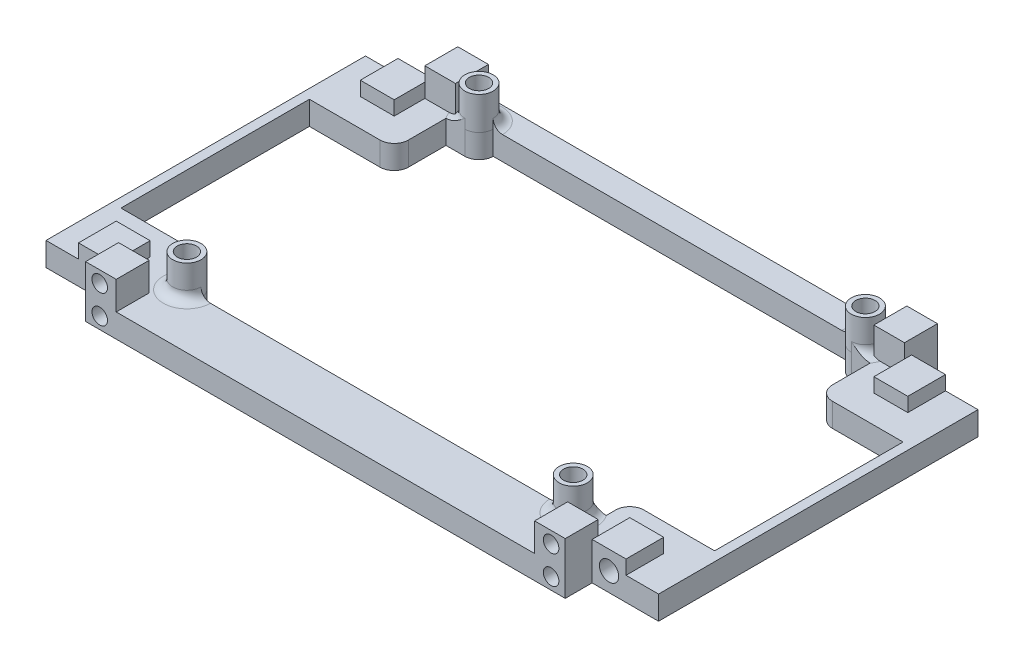
SolidWorks part; units mm, degrees
ref_plane "Front Plane" through (0, 0, 0) normal (0, 0, 1) x (1, 0, 0)
ref_plane "Top Plane" through (0, 0, 0) normal (0, 1, 0) x (1, 0, 0)
ref_plane "Right Plane" through (0, 0, 0) normal (1, 0, 0) x (0, 0, -1)
sketch "Sketch1" plane through (0, 0, 0) normal (0, 1, 0) x (1, 0, 0)
  line L0 (-65, -33.9) -> (-65, 33.9)
  line L1 (-65, -41) -> (65, -41) construction
  line L2 (-65, -41) -> (-65, 41) construction
  line L3 (-65, 41) -> (65, 41) construction
  line L4 (65, -41) -> (65, 41) construction
  line L5 (-65, -41) -> (65, 41) construction
  line L6 (-65, 41) -> (65, -41) construction
  line L7 (-65, 33.9) -> (-50.9, 33.9)
  line L8 (-50.9, 33.9) -> (-50.9, 41)
  line L9 (-50.9, 41) -> (50.9, 41)
  line L10 (50.9, 41) -> (50.9, 33.9)
  line L11 (50.9, 33.9) -> (65, 33.9)
  line L12 (65, 33.9) -> (65, -33.9)
  line L13 (65, -33.9) -> (50.9, -33.9)
  line L14 (50.9, -33.9) -> (50.9, -41)
  line L15 (50.9, -41) -> (-50.9, -41)
  line L16 (-50.9, -41) -> (-50.9, -33.9)
  line L17 (-50.9, -33.9) -> (-65, -33.9)
  point P0 (0, 0)
  dimension "D1" = 130
  dimension "D2" = 82
  dimension "D3" = 7.1
  dimension "D4" = 14.1
extrude "Boss-Extrude1" add sketch "Sketch1" along normal blind 5
sketch "Sketch3" plane through (0, 5, 0) normal (0, 1, 0) x (1, 0, 0)
  line L1 (-41, 34) -> (41, 34) construction
  line L2 (-41, 34) -> (-41, -28) construction
  line L3 (-41, -28) -> (41, -28) construction
  line L4 (41, 34) -> (41, -28) construction
  line L5 (-41, 34) -> (41, -28) construction
  line L6 (-41, -28) -> (41, 34) construction
  circle A0 centre (-41, -28) radius 3
  circle A1 centre (41, -28) radius 3
  circle A2 centre (41, 34) radius 3
  circle A3 centre (-41, 34) radius 3
  point P0 (0, 3)
  dimension "D4" = 6
  dimension "D1" = 82
  dimension "D2" = 62
  dimension "D3" = 3
sketch "Sketch2" plane through (0, 5, 0) normal (0, 1, 0) x (1, 0, 0)
  line L0 (-41, 31) -> (-38, 31)
  line L5 (-38, -28) -> (38, -28)
  line L6 (-41, -25) -> (-41, 31)
  line L7 (-38, 34) -> (38, 34)
  line L8 (41, -25) -> (41, 31)
  line L9 (-41, -28) -> (41, 34) construction
  line L10 (-41, 34) -> (41, -28) construction
  line L11 (-38, 31) -> (-38, 34)
  line L12 (38, 34) -> (38, 31)
  line L13 (38, 31) -> (41, 31)
  line L14 (41, -25) -> (38, -25)
  line L15 (38, -25) -> (38, -28)
  line L16 (-38, -28) -> (-38, -25)
  line L17 (-38, -25) -> (-41, -25)
  line L18 (41, -28) -> (-41, -28) construction
  line L19 (-41, -28) -> (-41, 34) construction
  line L20 (-41, 34) -> (41, 34) construction
  line L21 (41, 34) -> (41, -28) construction
  point P0 (0, 0)
  point P1 (0, 3)
  dimension "D1" = 3
extrude "Cut-Extrude1" cut sketch "Sketch2" against normal through all
extrude "Boss-Extrude2" add sketch "Sketch3" along normal blind 7
sketch "Sketch4" plane through (0, 12, 0) normal (0, 1, 0) x (1, 0, 0)
  circle A0 centre (-41, 34) radius 2.05
  circle A1 centre (41, 34) radius 2.05
  circle A2 centre (41, -28) radius 2.05
  circle A3 centre (-41, -28) radius 2.05
  dimension "D1" = 4.1
extrude "Cut-Extrude2" cut sketch "Sketch4" against normal through all and the other way through all
sketch "Sketch5" plane through (0, 5, 0) normal (0, 1, 0) x (1, 0, 0)
  line L0 (-41, -25) -> (-38, -25) construction
  line L1 (-41, 31) -> (-53, 31)
  line L2 (-41, 31) -> (-41, -25)
  line L3 (-41, -25) -> (-53, -25)
  line L4 (-53, 31) -> (-53, -25)
  line L5 (0, 34) -> (0, -28) construction
  line L6 (38, 34) -> (-38, 34) construction
  line L7 (-38, -28) -> (38, -28) construction
  line L8 (53, 31) -> (53, -25)
  line L9 (41, -25) -> (53, -25)
  line L10 (41, 31) -> (41, -25)
  line L11 (41, 31) -> (53, 31)
  dimension "D1" = 12
extrude "Cut-Extrude3" cut sketch "Sketch5" against normal through all
fillet "Fillet1" radius 3 4 edges at (38, 2.5, 25) (-38, 2.5, 25) (38, 2.5, -31) (-38, 2.5, -31)
sketch "Sketch6" plane through (0, 5, 0) normal (0, 1, 0) x (1, 0, 0)
  line L0 (38, 34) -> (-38, 34) construction
  line L1 (-25, 34) -> (25, 34)
  line L2 (-25, 34) -> (-25, 28)
  line L3 (-25, 28) -> (25, 28)
  line L4 (25, 34) -> (25, 28)
  line L5 (0, -28) -> (0, -41) construction
  line L6 (-38, -28) -> (38, -28) construction
  line L7 (-50.9, -41) -> (50.9, -41) construction
  line L8 (0, 28) -> (0, 41) construction
  line L9 (50.9, 41) -> (-50.9, 41) construction
  point P6 (0, 28)
  dimension "D1" = 50
sketch "Sketch7" plane through (0, 5, 0) normal (0, 1, 0) x (1, 0, 0)
  line L0 (0, 41) -> (0, -41) construction
  line L1 (50.9, 33.9) -> (58.1, 33.9)
  line L2 (50.9, 33.9) -> (50.9, 25.9)
  line L3 (50.9, 25.9) -> (58.1, 25.9)
  line L4 (58.1, 33.9) -> (58.1, 25.9)
  line L5 (50.9, 41) -> (-50.9, 41) construction
  line L6 (-50.9, -41) -> (50.9, -41) construction
  line L7 (-65, 0) -> (65, 0) construction
  line L8 (-65, 33.9) -> (-65, -33.9) construction
  line L9 (65, -33.9) -> (65, 33.9) construction
  dimension "D1" = 7.2
  dimension "D2" = 8
extrude "Boss-Extrude3" add sketch "Sketch7" along normal blind 3
sketch "Sketch8" plane through (0, 0, -33.9) normal (0, 0, -1) x (-1, 0, 0)
  line L0 (-58.1, 8) -> (-50.9, 0) construction
  circle A0 centre (-54.5, 4) radius 2.05
  dimension "D1" = 4.1
extrude "Cut-Extrude5" cut sketch "Sketch8" against normal blind 6
mirror "Mirror3" about plane through (0, 0, 0) normal (1, 0, 0) of "Cut-Extrude5", "Boss-Extrude3"
mirror "Mirror4" about plane through (0, 0, 0) normal (0, 0, 1) of "Mirror3"
sketch "Sketch10" plane through (0, 5, 0) normal (0, 1, 0) x (1, 0, 0)
  line L0 (50.9, 33.9) -> (50.9, 41) construction
  line L1 (-50.9, 41) -> (50.9, 41)
  line L2 (-50.9, 41) -> (-50.9, 40)
  line L3 (-50.9, 40) -> (50.9, 40)
  line L4 (50.9, 41) -> (50.9, 40)
  line L5 (-50.9, -33.9) -> (-50.9, -41) construction
  line L6 (50.9, -41) -> (-50.9, -41)
  line L7 (50.9, -41) -> (50.9, -40)
  line L8 (50.9, -40) -> (-50.9, -40)
  line L9 (-50.9, -41) -> (-50.9, -40)
  dimension "D1" = 1
  dimension "D2" = 1
extrude "Cut-Extrude7" cut sketch "Sketch10" against normal through all
fillet "Fillet5" radius 2 4 edges at (43.1213, 5, -36.1213) (43.1213, 5, 30.1213) (-43.1213, 5, 30.1213) (-43.1213, 5, -36.1213)
sketch "Sketch11" plane through (0, 5, 0) normal (0, 1, 0) x (1, 0, 0)
  line L0 (-45, 31) -> (-50.9, 31) construction
  line L1 (53, -25) -> (45, -25)
  line L2 (53, -25) -> (53, 31)
  line L3 (53, 31) -> (45, 31)
  line L4 (45, -25) -> (45, 31)
  line L5 (-45, -25) -> (-53, -25)
  line L6 (-45, -25) -> (-45, 31)
  line L7 (-45, 31) -> (-53, 31)
  line L8 (-53, -25) -> (-53, 31)
  point P11 (0, 0)
  point P12 (-48.5593, 28.3597)
extrude "Boss-Extrude4" add sketch "Sketch11" against normal up to surface (5 mm away) up to face at (0, 0, 0)
sketch "Sketch12" plane through (0, 5, 0) normal (0, 1, 0) x (1, 0, 0)
  line L0 (45, 31) -> (45, -25) construction
  line L1 (45, 20) -> (63, 20)
  line L2 (45, 20) -> (45, -20)
  line L3 (45, -20) -> (63, -20)
  line L4 (63, 20) -> (63, -20)
  line L5 (65, -33.9) -> (65, 33.9) construction
  point P6 (63, 0)
  point P9 (65, 0)
  dimension "D1" = 18
  dimension "D2" = 40
extrude "Cut-Extrude8" cut sketch "Sketch12" against normal through all and the other way through all
mirror "Mirror7" about plane through (0, 0, 0) normal (1, 0, 0) of "Cut-Extrude8"
fillet "Fillet6" radius 3 4 edges at (45, 2.5, -20) (45, 2.5, 20) (-45, 2.5, -20) (-45, 2.5, 20)
sketch "Sketch13" plane through (0, 5, 0) normal (0, 1, 0) x (1, 0, 0)
  line L0 (50.9, 33.9) -> (50.9, 40) construction
  line L1 (-50.9, 40) -> (50.9, 40)
  line L2 (-50.9, 40) -> (-50.9, 39.4)
  line L3 (-50.9, 39.4) -> (50.9, 39.4)
  line L4 (50.9, 40) -> (50.9, 39.4)
  line L5 (-50.9, -33.9) -> (-50.9, -40) construction
  line L6 (50.9, -40) -> (-50.9, -40)
  line L7 (50.9, -40) -> (50.9, -39.6)
  line L8 (50.9, -39.6) -> (-50.9, -39.6)
  line L9 (-50.9, -40) -> (-50.9, -39.6)
  dimension "D1" = 0.6
  dimension "D2" = 0.4
extrude "Cut-Extrude9" cut sketch "Sketch13" against normal through all both and the other way through all
sketch "Sketch14" plane through (0, 5, 0) normal (0, 1, 0) x (1, 0, 0)
  line L1 (-50.9, -39.6) -> (-44.4, -39.6)
  line L2 (-50.9, -39.6) -> (-50.9, -32.6)
  line L3 (-50.9, -32.6) -> (-44.4, -32.6)
  line L4 (-44.4, -39.6) -> (-44.4, -32.6)
  line L5 (-50.9, 39.4) -> (-44.4, 39.4)
  line L6 (-50.9, 39.4) -> (-50.9, 32.4)
  line L7 (-50.9, 32.4) -> (-44.4, 32.4)
  line L8 (-44.4, 39.4) -> (-44.4, 32.4)
  dimension "D1" = 6.5
  dimension "D2" = 7
extrude "Boss-Extrude5" add sketch "Sketch14" along normal blind 6
sketch "Sketch15" plane through (0, 0, 39.6) normal (0, 0, 1) x (1, 0, 0)
  line L0 (-44.4, 5) -> (-44.4, 0) construction
  line L1 (50.9, 0) -> (-50.9, 0) construction
  line L3 (-50.9, 0) -> (-50.9, 11) construction
  circle A0 centre (-47.9, 2.5) radius 1.65
  circle A1 centre (-47.9, 8.5) radius 1.65
  point P4 (-44.4, 2.5)
  dimension "D1" = 3.3
  dimension "D2" = 3
  dimension "D3" = 6
extrude "Cut-Extrude10" cut sketch "Sketch15" against normal blind 6
sketch "Sketch16" plane through (0, 0, -39.4) normal (0, 0, -1) x (-1, 0, 0)
  circle A0 centre (47.9, 8.5) radius 1.65 construction
  circle A1 centre (47.9, 2.5) radius 1.65 construction
  circle A2 centre (47.9, 8.5) radius 1.65
  circle A3 centre (47.9, 2.5) radius 1.65
extrude "Cut-Extrude11" cut sketch "Sketch16" against normal blind 6
mirror "Mirror8" about plane through (0, 0, 0) normal (1, 0, 0) of "Cut-Extrude10", "Cut-Extrude11", "Boss-Extrude5"
